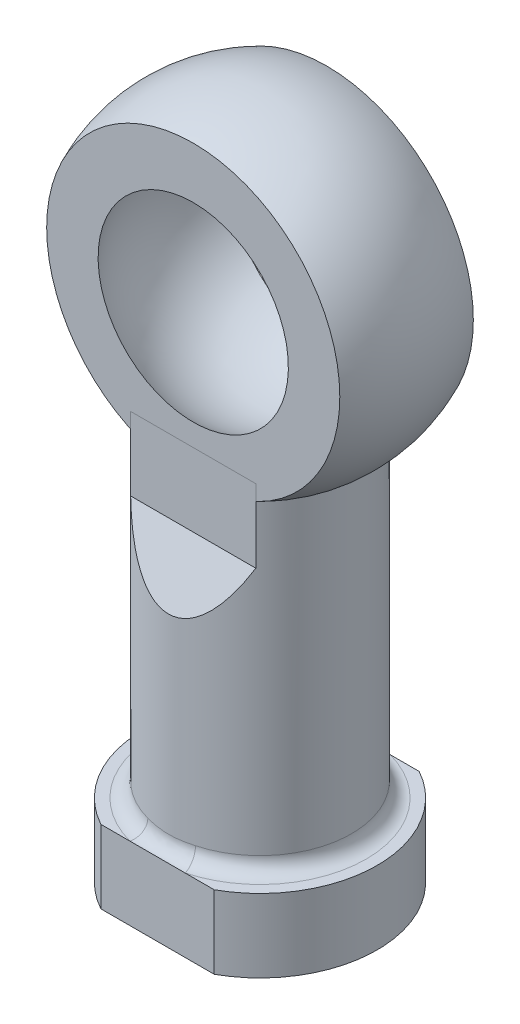
SolidWorks part; units mm, degrees
material "Plain Carbon Steel"
ref_plane "Front Plane" through (0, 0, 0) normal (0, 0, 1) x (1, 0, 0)
ref_plane "Top Plane" through (0, 0, 0) normal (0, 1, 0) x (1, 0, 0)
ref_plane "Right Plane" through (0, 0, 0) normal (1, 0, 0) x (0, 0, -1)
sketch "Sketch2" plane through (0, 0, 0) normal (1, 0, 0) x (0, 0, -1)
  line L0 (0, 15.4744) -> (0, -15.7624) construction
  line L1 (0, 7.938) -> (0, -7.938)
  arc A0 (0, 7.938) -> (0, -7.938) centre (0, 0) cw
  point P6 (0, -14.2606)
  dimension "D1" = 7.938
sketch "Sketch3" plane through (0, 0, 0) normal (1, 0, 0) x (0, 0, -1)
  line L0 (-8.1466, 0) -> (8.1466, 0) construction
  line L1 (0, 31.115) -> (0, -31.115) construction
  line L2 (-4.56, 10.0103) -> (-4.56, 0)
  line L3 (-4.56, 0) -> (4.56, 0)
  line L4 (4.56, 0) -> (4.56, 10.0103)
  arc A0 (-4.56, 10.0103) -> (4.56, 10.0103) centre (0, 0) cw
  point P8 (0, 11)
  dimension "D2" = 9.12
  dimension "D1" = 11
revolve "Revolve2" add sketch "Sketch3"
revolve "Cut-Revolve2" cut sketch "Sketch2" angle 360 about L0
sketch "Sketch4" plane through (0, 0, 0) normal (1, 0, 0) x (0, 0, -1)
  line L0 (0, -11) -> (0, -35.6534) construction
  arc A0 (-4.56, -10.0103) -> (4.56, -10.0103) centre (0, 0) ccw construction
ref_plane "Plane1" through (0, -11, 0) normal (0, 1, 0) x (-1, 0, 0)
sketch "Sketch5" plane through (0, -11, 0) normal (0, 1, 0) x (-1, 0, 0)
  circle A0 centre (0, 0) radius 6.25
  circle A1 centre (0, 0) radius 3.4
  dimension "D1" = 12.5
  dimension "D2" = 6.8
extrude "ExtrudeRodHole" add sketch "Sketch5" against normal blind 25 and the other way blind 3 separate body
cosmetic thread "Cosmetic Thread1" parameters "D1"=28, "D2"=8
sketch "Sketch7" plane through (0, -36, 0) normal (0, -1, 0) x (1, 0, 0)
  line L0 (-3.873, 7) -> (3.873, 7)
  line L1 (-3.873, -7) -> (3.873, -7)
  circle A0 centre (0, 0) radius 3.4 construction
  circle A1 centre (0, 0) radius 3.4
  arc A2 (-3.873, 7) -> (-3.873, -7) centre (0, 0) ccw
  arc A3 (3.873, -7) -> (3.873, 7) centre (0, 0) ccw
  dimension "D1" = 16
  dimension "D2" = 14
extrude "Boss-Extrude1" add sketch "Sketch7" against normal blind 5
sketch "Sketch6" plane through (0, 0, 0) normal (1, 0, 0) x (0, 0, -1)
  line L0 (0, 18.0632) -> (0, -54.6469) construction
  line L1 (10.0987, 0) -> (-10.0987, 0) construction
  line L2 (0, -11) -> (0, -35.6534) construction
  point P5 (0, 0)
  point P6 (0, -15)
fillet "Fillet1" radius 1 1 edges at (0, -31, -6.25)
sketch "Sketch8" plane through (0, 0, 0) normal (1, 0, 0) x (0, 0, -1)
  line L0 (0, 0) -> (0, -37.9096) construction
  line L1 (-4.56, 0) -> (-4.56, -13)
  line L2 (-4.56, 10.0103) -> (-4.56, -10.0103) construction
  line L3 (-4.56, -13) -> (-6.25, -17)
  line L4 (-6.25, -8) -> (-6.25, -30.0318) construction
  line L5 (-6.25, -17) -> (-14.3389, -17)
  line L6 (-14.3389, -17) -> (-14.3389, 16.9811)
  line L7 (-14.3389, 16.9811) -> (14.3389, 16.9811)
  line L8 (-4.56, 0) -> (-4.56, 14.7187)
  line L9 (-4.56, 14.7187) -> (4.56, 14.7187)
  line L10 (4.56, 0) -> (4.56, 14.7187)
  line L11 (4.56, 0) -> (4.56, -13)
  line L12 (4.56, -13) -> (6.25, -17)
  line L13 (6.25, -17) -> (14.3389, -17)
  line L14 (14.3389, -17) -> (14.3389, 16.9811)
  point P16 (0, 14.7187)
  point P21 (0, 16.9811)
  dimension "D1" = 13
  dimension "D2" = 4
extrude "Cut-Extrude1" cut sketch "Sketch8" against normal through all and the other way through all
